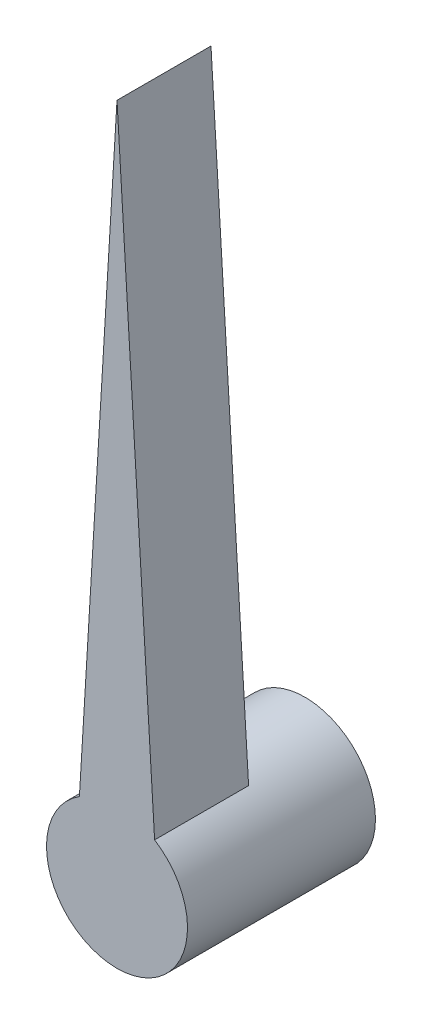
SolidWorks part; units mm, degrees
ref_plane "Front Plane" through (0, 0, 0) normal (0, 0, 1) x (1, 0, 0)
ref_plane "Top Plane" through (0, 0, 0) normal (0, 1, 0) x (1, 0, 0)
ref_plane "Right Plane" through (0, 0, 0) normal (1, 0, 0) x (0, 0, -1)
sketch "Sketch1" plane through (0, 0, 0) normal (0, 0, 1) x (1, 0, 0)
  circle A0 centre (0, 0) radius 3.81
  dimension "D1" = 7.62
extrude "Boss-Extrude2" add sketch "Sketch1" along normal blind 10.16
sketch "Sketch3" plane through (0, 0, 0) normal (0, 0, -1) x (-1, 0, 0)
  circle A0 centre (0, 0) radius 2.54
  dimension "D1" = 5.08
extrude "Cut-Extrude1" cut sketch "Sketch3" against normal blind 5.08
sketch "Sketch4" plane through (0, 0, 10.16) normal (0, 0, 1) x (1, 0, 0)
  line L0 (-2.0323, 3.2227) -> (2.0323, 3.2227)
  line L1 (0, 36.83) -> (-2.0323, 3.2227)
  line L2 (0, 36.83) -> (2.0323, 3.2227)
  circle A0 centre (0, 0) radius 3.81 construction
extrude "Boss-Extrude3" add sketch "Sketch4" against normal blind 5.08
